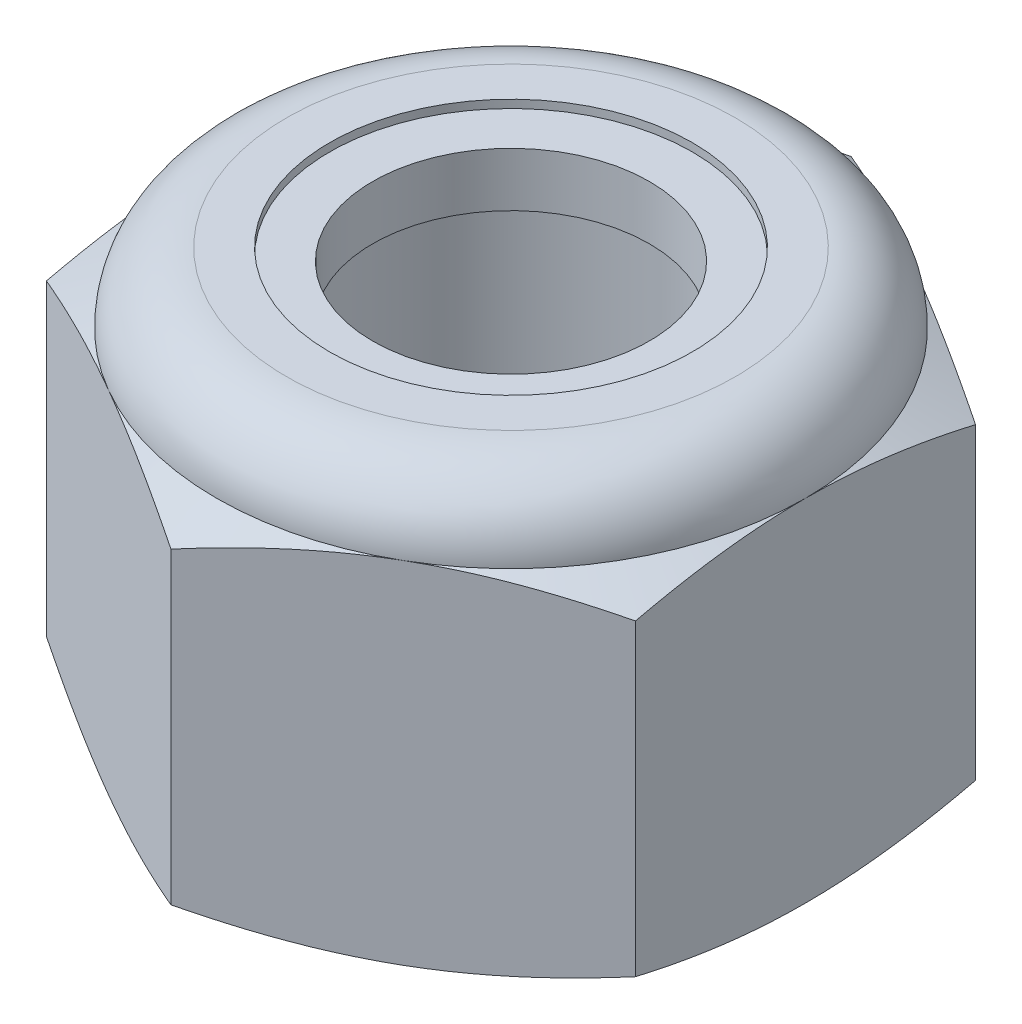
SolidWorks part; units mm, degrees
ref_plane "Front" through (0, 0, 0) normal (0, 0, 1) x (1, 0, 0)
ref_plane "Top" through (0, 0, 0) normal (0, 1, 0) x (1, 0, 0)
ref_plane "Right" through (0, 0, 0) normal (1, 0, 0) x (0, 0, -1)
sketch "Sketch1" plane through (0, 0, 0) normal (0, 1, 0) x (1, 0, 0)
  line L1 (0, 6.4158) -> (-5.5563, 3.2079)
  line L2 (-5.5563, 3.2079) -> (-5.5563, -3.2079)
  line L3 (-5.5563, -3.2079) -> (0, -6.4158)
  line L4 (0, -6.4158) -> (5.5562, -3.2079)
  line L5 (5.5562, -3.2079) -> (5.5562, 3.2079)
  line L6 (5.5562, 3.2079) -> (0, 6.4158)
  circle A0 centre (0, 0) radius 5.5563 construction
  dimension "Hex Flats" = 11.1125
extrude "Extrude1" add sketch "Sketch1" along normal blind 7.9375
sketch "Sketch2" plane through (0, 0, 0) normal (1, 0, 0) x (0, 0, -1)
  line L0 (-3.175, 0) -> (-3.175, 7.9375) construction
  line L1 (0, 0) -> (3.175, 0)
  line L2 (0, 0) -> (0, 7.9375)
  line L3 (0, 7.9375) -> (3.175, 7.9375)
  line L4 (3.175, 0) -> (3.175, 7.9375)
  line L5 (-3.2079, 7.9375) -> (3.2079, 7.9375) construction
  line L7 (0, -3.175) -> (0, 0) construction
  dimension "Thread Dia" = 6.35
revolve "Revolve1" add sketch "Sketch2" angle 360 about L7
sketch "Sketch3" plane through (0, 0, 0) normal (1, 0, 0) x (0, 0, -1)
  line L0 (3.175, 7.9375) -> (-3.175, 7.9375) construction
  line L1 (-3.175, 7.9375) -> (-3.175, 6.6675) construction
  line L2 (-3.175, 6.6675) -> (3.175, 7.9375) construction
  line L3 (3.175, 7.9375) -> (3.2061, 7.7818) construction
  line L4 (3.2061, 7.7818) -> (3.4241, 6.6922)
  line L5 (3.4241, 6.6922) -> (2.6722, 6.9465)
  line L6 (2.6722, 6.9465) -> (2.6099, 7.2579)
  line L7 (2.6099, 7.2579) -> (3.2061, 7.7818)
  line L8 (2.641, 7.1022) -> (3.3151, 7.237) construction
  line L9 (3.175, 7.9375) -> (3.175, 7.209) construction
  line L10 (3.175, 7.209) -> (-3.175, 5.939) construction
  line L11 (-3.175, 5.939) -> (-3.175, 6.6675) construction
  line L12 (-0.2727, 7.9375) -> (0.2727, 5.2105) construction
  line L13 (-3.175, 0) -> (-3.175, 7.9375) construction
  line L14 (0, 7.9375) -> (3.175, 7.9375) construction
  line L15 (3.175, 0) -> (3.175, 7.9375) construction
  point P13 (0, 6.574)
  dimension "D2" = 0.3175
  dimension "Thread Pitch" = 1.27
  dimension "D4" = 60
  dimension "D5" = 1.27
revolve "Cut-Revolve1" [suppressed] cut sketch "Sketch3" angle 360 about L12
pattern_linear "LPattern1" [suppressed] count 6 spacing 1.27 along (0, -1, 0) count 2 spacing 1.27 along (0, 1, 0) of bodies 110
sketch "Sketch4" plane through (0, 0, 0) normal (1, 0, 0) x (0, 0, -1)
  line L0 (0, 7.9375) -> (3.175, 7.9375)
  line L1 (3.175, 7.9375) -> (2.6099, 7.674)
  line L2 (2.6099, 7.674) -> (2.6099, 0.2635)
  line L3 (2.6099, 0.2635) -> (3.175, 0)
  line L4 (3.175, 0) -> (0, 0)
  line L5 (0, 0) -> (0, 7.9375)
  line L6 (3.175, 0) -> (3.175, 7.9375) construction
  line L7 (0, 7.9375) -> (3.175, 7.9375) construction
  line L8 (0, 0) -> (3.175, 0) construction
  line L9 (0, 0) -> (0, 7.9375) construction
  line L10 (0, 7.9375) -> (0, 8.561) construction
  dimension "D1" = 25
revolve "Cut-Revolve2" cut sketch "Sketch4" angle 360 about L10
combine bodies "Combine1" operation type subtract main body 112 bodies to subtract 109
sketch "Sketch5" plane through (0, 0, 0) normal (1, 0, 0) x (0, 0, -1)
  line L0 (0, 0) -> (5.5563, 0)
  line L1 (5.5563, 0) -> (6.4158, 0.4008)
  line L2 (6.4158, 0.4008) -> (6.4158, 6.2138)
  line L3 (6.4158, 6.2138) -> (5.5563, 6.6146)
  line L4 (4.2333, 7.9375) -> (4.2333, 9.2075)
  line L5 (4.2333, 9.2075) -> (7.6858, 9.2075)
  line L6 (7.6858, 9.2075) -> (7.6858, -1.27)
  line L7 (7.6858, -1.27) -> (0, -1.27)
  line L8 (0, -1.27) -> (0, 0)
  line L9 (5.5563, 6.6146) -> (5.5563, 0) construction
  line L10 (0, 0) -> (3.175, 0) construction
  line L13 (6.4158, 3.3073) -> (7.6858, 3.3073) construction
  line L14 (6.4158, 7.9375) -> (6.4158, 0) construction
  line L15 (0, 0) -> (0, 9.2075) construction
  line L20 (0, 9.2075) -> (4.2333, 9.2075) construction
  line L22 (0, 7.9375) -> (3.175, 7.9375) construction
  arc A0 (5.5563, 6.6146) -> (4.2333, 7.9375) centre (4.2333, 6.6146) ccw
  dimension "D1" = 25
  dimension "D2" = 1.27
  dimension "D3" = 7.9375
  dimension "D4" = 1.3229
revolve "Cut-Revolve3" cut sketch "Sketch5" angle 360 about L15
sketch "Sketch6" plane through (0, 0, 0) normal (1, 0, 0) x (0, 0, -1)
  line L0 (0, 6.6146) -> (5.4039, 6.6146)
  line L1 (4.2333, 7.7851) -> (3.4216, 7.7851)
  line L2 (0, 9.2075) -> (0, 6.6146)
  line L3 (3.4216, 9.2075) -> (0, 9.2075)
  line L4 (0, 9.2075) -> (4.2333, 9.2075) construction
  line L5 (0, 0) -> (0, 9.2075) construction
  line L6 (0, 9.2075) -> (0, 44.323) construction
  line L7 (3.4216, 7.7851) -> (3.4216, 9.2075)
  line L8 (4.2333, 7.9375) -> (4.2333, 7.7851) construction
  line L9 (3.4216, 7.7851) -> (2.6099, 7.7851) construction
  line L10 (2.6099, 7.7851) -> (2.6099, 7.674) construction
  arc A0 (5.4039, 6.6146) -> (4.2333, 7.7851) centre (4.2333, 6.6146) ccw
  arc A1 (5.5563, 6.6146) -> (4.2333, 7.9375) centre (4.2333, 6.6146) ccw construction
  dimension "D1" = 0.1524
revolve "Cut-Revolve4" cut sketch "Sketch6" angle 360 about L6
sketch "Sketch7" plane through (0, 0, 0) normal (1, 0, 0) x (0, 0, -1)
  line L0 (2.6099, 6.6908) -> (5.325, 6.6908)
  line L1 (4.2333, 7.7089) -> (2.6099, 7.7089)
  line L2 (2.6099, 7.7089) -> (2.6099, 6.6908)
  line L3 (2.6099, 6.6908) -> (0, 6.6908) construction
  line L4 (0, 6.6908) -> (0, 7.7089) construction
  line L5 (0, 7.7089) -> (2.6099, 7.7089) construction
  line L6 (2.6099, 6.6908) -> (2.6099, 6.6146) construction
  line L7 (0, 6.6146) -> (5.4039, 6.6146) construction
  line L8 (4.2333, 7.7089) -> (4.2333, 7.7851) construction
  arc A0 (5.325, 6.6908) -> (4.2333, 7.7089) centre (4.2333, 6.6146) ccw
  arc A2 (5.4039, 6.6146) -> (4.2333, 7.7851) centre (4.2333, 6.6146) ccw construction
  dimension "D1" = 0.0762
revolve "Revolve2" add sketch "Sketch7" angle 360 about L4
equation "\"D1@Sketch3\"=\"Thread Pitch@Sketch3\"/8"
equation "\"D2@Sketch3\"=\"Thread Pitch@Sketch3\"/4"
equation "\"D5@Sketch3\"=\"Thread Pitch@Sketch3\""
equation "\"D4@LPattern1\"=\"Thread Pitch@Sketch3\""
equation "\"D3@LPattern1\"=\"Thread Pitch@Sketch3\""
equation "\"D1@LPattern1\"=\"Height@Extrude1\"/\"Thread Pitch@Sketch3\""
equation "\"D4@Sketch5\"=\"Height@Extrude1\"/6"
